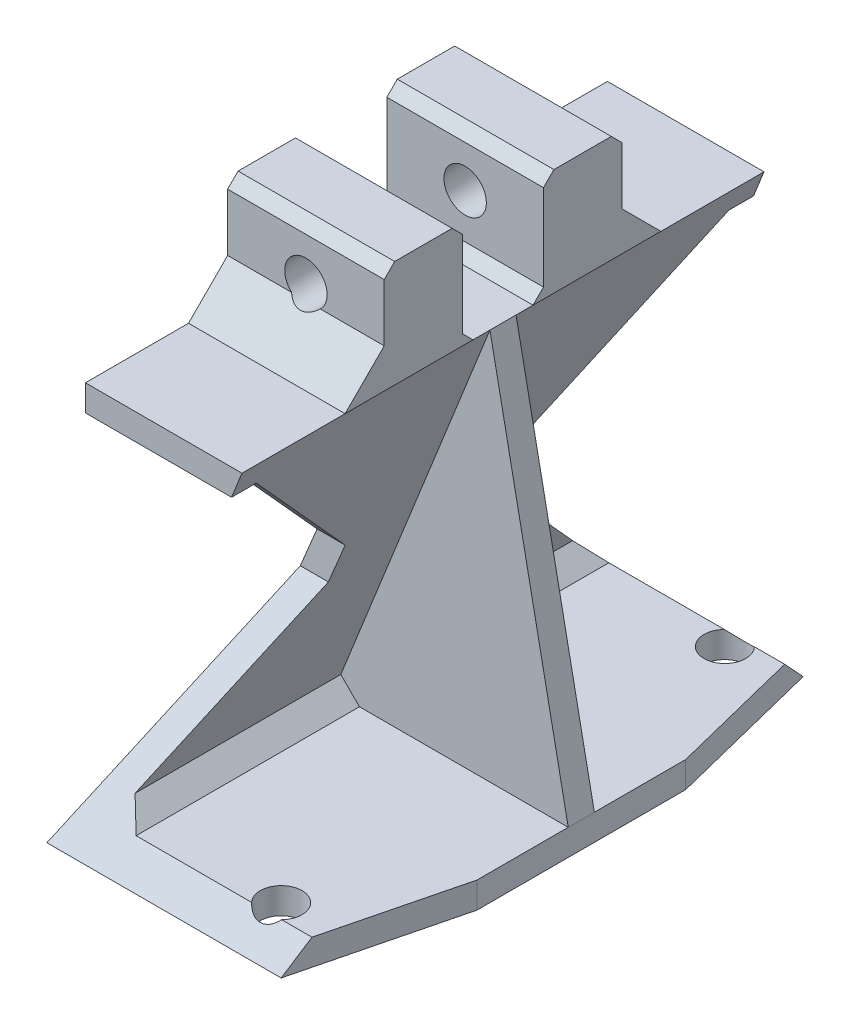
SolidWorks part; units mm, degrees
ref_plane "Front Plane" through (0, 0, 0) normal (0, 0, 1) x (1, 0, 0)
ref_plane "Top Plane" through (0, 0, 0) normal (0, 1, 0) x (1, 0, 0)
ref_plane "Right Plane" through (0, 0, 0) normal (1, 0, 0) x (0, 0, -1)
sketch "Sketch1" plane through (0, 0, 0) normal (0, 0, 1) x (1, 0, 0)
  line L0 (0, 0) -> (12, 0)
  line L1 (12, 0) -> (0, -30)
  line L2 (0, -30) -> (18, -30)
  line L3 (0, -2) -> (9.0459, -2)
  line L4 (9.0459, -2) -> (-2.9541, -32)
  line L5 (-2.9541, -32) -> (18, -32)
  line L6 (0, 0) -> (0, -2)
  line L7 (18, -30) -> (18, -32)
  point P3 (0, 0)
  dimension "D1" = 12
  dimension "D2" = 18
  dimension "D3" = 30
  dimension "D4" = 2
extrude "Boss-Extrude1" add sketch "Sketch1" along normal blind 40
sketch "Sketch2" plane through (0, 0, 0) normal (-1, 0, 0) x (0, 0, 1)
  line L0 (0, 0) -> (15.0997, -16)
  line L1 (15.0997, -16) -> (0, -32)
  line L4 (40, 0) -> (24.9003, -16)
  line L5 (24.9003, -16) -> (40, -32)
  line L6 (0, 0) -> (0, -2) construction
  line L7 (40, -2) -> (0, -2) construction
  line L10 (0, -2) -> (0, -32)
  line L11 (0, -32) -> (40, -32)
  line L12 (40, -32) -> (40, -2)
  line L13 (40, -2) -> (0, -2)
  line L14 (0, -2) -> (0, -32)
  line L15 (0, -32) -> (40, -32)
  line L16 (40, -32) -> (40, -2)
  line L17 (40, -2) -> (0, -2)
  line M9 (0, -2) -> (40, -2)
  dimension "D1" = 22
  dimension "D2" = 22
  dimension "D3" = 22
  dimension "D4" = 0
extrude "Cut-Extrude1" cut sketch "Sketch2" against normal blind 30 and the other way blind 30 contours L14 L1 L0 M9 | L5 L16 L4 M9 region at (0, -16.1155, 5.0679) region at (0, -16.1155, 34.9321)
chamfer "Chamfer1" distance 2 angle 45 4 edges at (4.523, -16, 15.0997) (4.523, -16, 24.9003) (0, -30, 20) (9.0459, -2, 20) first distance on face at (7.323, -9, 8.4936) first distance on face at (7.323, -9, 31.5064) first distance on face at (9, -30, 20) first distance on face at (7.8615, -2, 20)
sketch "Sketch3" plane through (0, -32, 0) normal (0, -1, 0) x (1, 0, 0)
  line L0 (12, 37) -> (12, 3) construction
  line L1 (18, 40) -> (18, 0) construction
  line L2 (15, 40) -> (18, 28)
  line L3 (-2.9541, 40) -> (18, 40) construction
  line L4 (15, 0) -> (18, 12)
  line L5 (-2.9541, 0) -> (18, 0) construction
  circle A0 centre (12, 37) radius 1.6
  circle A1 centre (12, 3) radius 1.6
  point P6 (18, 20)
  point P7 (12, 20)
  line M4 (-2.9541, 0) -> (18, 0)
  line M5 (18, 0) -> (18, 40)
  line M6 (18, 40) -> (-2.9541, 40)
  dimension "D1" = 3.2
  dimension "D2" = 3.2
  dimension "D3" = 34
  dimension "D4" = 6
  dimension "D5" = 3
  dimension "D6" = 3
  dimension "D7" = 12
  dimension "D8" = 12
extrude "Cut-Extrude2" cut sketch "Sketch3" against normal blind 10 contours A0 | L2 M6 M5 | L4 M4 M5 | A1 region at (17, -32, 36) region at (17, -32, 4) region at (12, -32, 37) region at (12, -32, 3)
sketch "Sketch4" plane through (0, 0, 0) normal (-1, 0, 0) x (0, 0, 1)
  line L0 (40, 0) -> (0, 0) construction
  line L1 (10.9, 0) -> (16.9, 0)
  line L2 (10.9, 0) -> (10.9, 8.2)
  line L3 (10.9, 8.2) -> (16.9, 8.2)
  line L4 (16.9, 0) -> (16.9, 8.2)
  line L5 (10.9, 0) -> (16.9, 8.2) construction
  line L6 (10.9, 8.2) -> (16.9, 0) construction
  line L7 (13.9, 4.1) -> (26.1, 4.1) construction
  line L8 (29.1, 0) -> (23.1, 0)
  line L9 (29.1, 0) -> (29.1, 8.2)
  line L10 (29.1, 8.2) -> (23.1, 8.2)
  line L11 (23.1, 0) -> (23.1, 8.2)
  line L12 (29.1, 0) -> (23.1, 8.2) construction
  line L13 (29.1, 8.2) -> (23.1, 0) construction
  point P4 (13.9, 4.1)
  point P11 (26.1, 4.1)
  point P14 (20, 0)
  point P15 (20, 4.1)
  dimension "D1" = 6.2
  dimension "D2" = 8.2
  dimension "D3" = 8.2
  dimension "D4" = 6
  dimension "D5" = 6
extrude "Boss-Extrude2" add sketch "Sketch4" against normal blind 12
chamfer "Chamfer2" distance 3 angle 45 2 edges at (6, 0, 10.9) (6, 0, 29.1)
chamfer "Chamfer3" distance 0.8 angle 45 6 edges at (6, 0, 16.9) (6, 0, 23.1) (6, 8.2, 29.1) (6, 8.2, 23.1) (6, 8.2, 16.9) (6, 8.2, 10.9)
sketch "Sketch5" plane through (0, 0, 29.1) normal (0, 0, 1) x (1, 0, 0)
  line L0 (12, 7.4) -> (0, 7.4) construction
  line L1 (12, 0) -> (0, 0) construction
  circle A0 centre (6, 4.2) radius 1.625
  point P4 (6, 7.4)
  dimension "D1" = 3.25
  dimension "D2" = 4.2
extrude "Cut-Extrude3" cut sketch "Sketch5" against normal through all both and the other way through all
ref_plane "Plane1" through (0, 0, 20) normal (0, 0, 1) x (1, 0, 0)
sketch "Sketch8" plane through (0, 0, 20) normal (0, 0, 1) x (1, 0, 0)
  line L0 (12, 0) -> (18, -30)
rib "Rib1" sketch "Sketch8" sketch "Sketch8" thickness 2 extrusion direction parallel to sketch draft on no parameters "D1"=2
